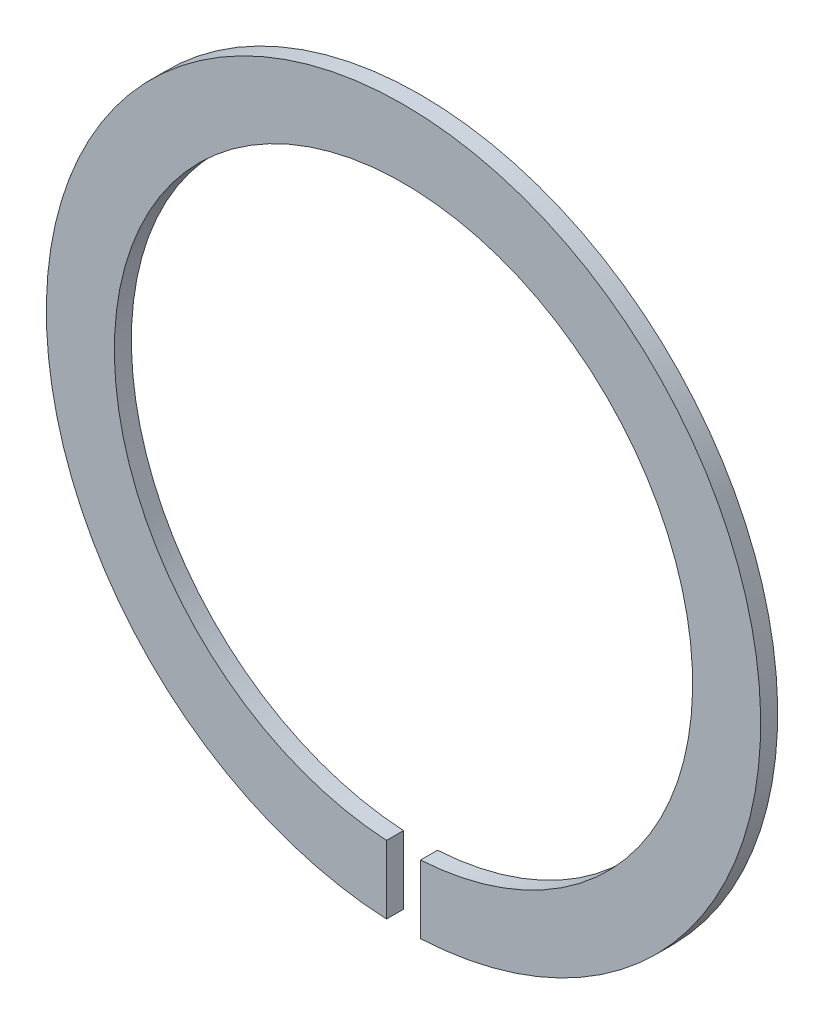
SolidWorks part; units mm, degrees
ref_plane "Plan de face" through (0, 0, 0) normal (0, 0, 1) x (1, 0, 0)
ref_plane "Plan de dessus" through (0, 0, 0) normal (0, 1, 0) x (1, 0, 0)
ref_plane "Plan de droite" through (0, 0, 0) normal (1, 0, 0) x (0, 0, -1)
sketch "Esquisse2" plane through (0, 0, 0) normal (0, 0, 1) x (1, 0, 0)
  line L0 (0, 0) -> (0, -4.3237) construction
  line L1 (0.5, -8.4853) -> (0.5, -10.4881)
  line L2 (-0.5, -8.4853) -> (-0.5, -10.4881)
  arc A0 (0.5, -10.4881) -> (-0.5, -10.4881) centre (0, 0) ccw
  arc A1 (0.5, -8.4853) -> (-0.5, -8.4853) centre (0, 0) ccw
  dimension "D1" = 21
  dimension "D2" = 17
  dimension "D3" = 0.5
extrude "Boss.-Extru.1" add sketch "Esquisse2" along normal blind 0.5
